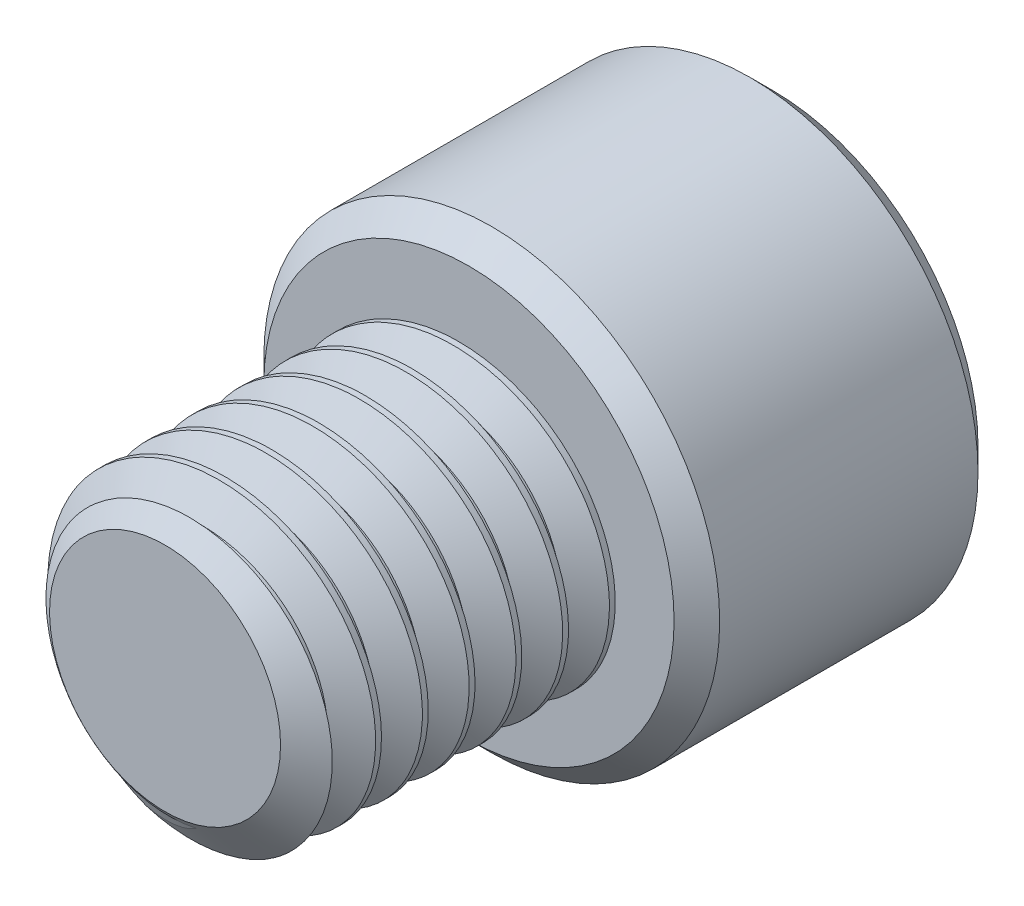
SolidWorks part; units mm, degrees
other "DetailItem1"
ref_plane "Front Plane" through (0, 0, 0) normal (0, 0, 1) x (1, 0, 0)
ref_plane "Top Plane" through (0, 0, 0) normal (0, 1, 0) x (1, 0, 0)
ref_plane "Right Plane" through (0, 0, 0) normal (1, 0, 0) x (0, 0, -1)
sketch "Sketch1" plane through (0, 0, 0) normal (0, 0, 1) x (1, 0, 0)
  circle A0 centre (0, 0) radius 6.35
  dimension "OD" = 12.7
extrude "Extrude1" add sketch "Sketch1" against normal blind 12.7
sketch "Sketch2" plane through (0, 0, 0) normal (0, 0, 1) x (1, 0, 0)
  circle A0 centre (0, 0) radius 6.35 construction
  circle A1 centre (0, 0) radius 6.35
curve "Helix/Spiral1" pitch 1.9538 height 14.6538 turns 7.5 parameters "pitch"=1.9538
sketch "Sketch3" plane through (0, 0, 0) normal (1, 0, 0) x (0, 0, -1)
  line L0 (-1.7096, 6.35) -> (-0.9769, 5.0809)
  line L1 (-0.9769, 5.0809) -> (-0.7327, 5.0809)
  line L2 (-0.7327, 5.0809) -> (0, 6.35)
  line L3 (-1.7096, 6.35) -> (0, 6.35)
  line L4 (-0.8548, 6.35) -> (-0.8548, 5.0809) construction
  line L5 (-1.3433, 5.7155) -> (-0.3663, 5.7155) construction
  line L6 (0, 6.35) -> (0, -6.35) construction
  dimension "D1" = 0.2442
  dimension "D2" = 0.9769
  dimension "D3" = 60
sweep "Cut-Sweep1" cut profiles "Sketch3" path "Helix/Spiral1"
sketch "Sketch4" plane through (0, 0, 0) normal (1, 0, 0) x (0, 0, -1)
  line L0 (1.0665, 6.35) -> (0, 4.8269)
  line L1 (0, 4.8269) -> (0, 6.35)
  line L2 (1.0665, 6.35) -> (0, 6.35)
  line L3 (-1.7096, 6.35) -> (0, 6.35) construction
  line L4 (0, 0) -> (7.0209, 0) construction
  dimension "D1" = 55
  dimension "D2" = 0.254
revolve "Cut-Revolve1" cut sketch "Sketch4" angle 360 about L4
sketch "Sketch6" plane through (0, 0, -12.7) normal (0, 0, -1) x (-1, 0, 0)
  circle A0 centre (0, 0) radius 9.525
  dimension "head dia" = 19.05
extrude "Extrude2" add sketch "Sketch6" along normal blind 12.7
sketch "Sketch7" plane through (0, 0, -25.4) normal (0, 0, -1) x (-1, 0, 0)
  line L1 (0, 5.4993) -> (-4.7625, 2.7496)
  line L2 (-4.7625, 2.7496) -> (-4.7625, -2.7496)
  line L3 (-4.7625, -2.7496) -> (0, -5.4993)
  line L4 (0, -5.4993) -> (4.7625, -2.7496)
  line L5 (4.7625, -2.7496) -> (4.7625, 2.7496)
  line L6 (4.7625, 2.7496) -> (0, 5.4993)
  circle A0 centre (0, 0) radius 4.7625 construction
  dimension "hex dia" = 9.525
extrude "Cut-Extrude1" cut sketch "Sketch7" against normal blind 7.1438
sketch "Sketch8" plane through (0, 0, -25.4) normal (0, 0, -1) x (-1, 0, 0)
  circle A0 centre (0, 0) radius 5.4993
extrude "Cut-Extrude2" cut sketch "Sketch8" against normal through all draft 45
chamfer "Chamfer1" distance 0.9525 angle 45 2 edges at (-9.525, 0, -25.4) (-9.525, 0, -12.7)
sketch "Sketch10" plane through (0, 0, -12.7) normal (0, 0, 1) x (1, 0, 0)
  circle A1 centre (0, 0) radius 6.35
  circle A2 centre (0, 0) radius 6.35
  dimension "D1" = 0
ref_plane "Plane1" through (0, 0, -19.05) normal (0, 0, 1) x (1, 0, 0)
extrude "partial thread" [suppressed] add sketch "Sketch10" along normal up to surface (31.75 mm away) separate body
chamfer "Chamfer2" [suppressed] distance 0.254 angle 45
combine bodies "Combine1" [suppressed] operation type add bodies to combine 107 108
sketch "Sketch9" plane through (0, 0, 0) normal (1, 0, 0) x (0, 0, -1)
  line L0 (0, 6.35) -> (0, -6.35) construction
  line L1 (4.8846, 6.35) -> (4.8846, -6.35) construction
  dimension "D1" = 4.8846
  dimension "D4" = 0.635
  dimension "D5" = 0.3302
equation "\"D3@Helix/Spiral1\" = \"screw length@Extrude1\"+\"pitch@Helix/Spiral1\""
equation "\"D1@Sketch3\" = \"pitch@Helix/Spiral1\"*.125"
equation "\"D2@Sketch3\" = \"pitch@Helix/Spiral1\"*.5"
equation "\"D1@Cut-Extrude1\" = \"hex dia@Sketch7\"*.75"
equation "\"D1@Chamfer1\" = \"head dia@Sketch6\"*.05"
equation "\"D1@Sketch9\" = \"pitch@Helix/Spiral1\"*2.5"
equation "\"D1@Chamfer2\"=\"OD@Sketch1\"*.02"
